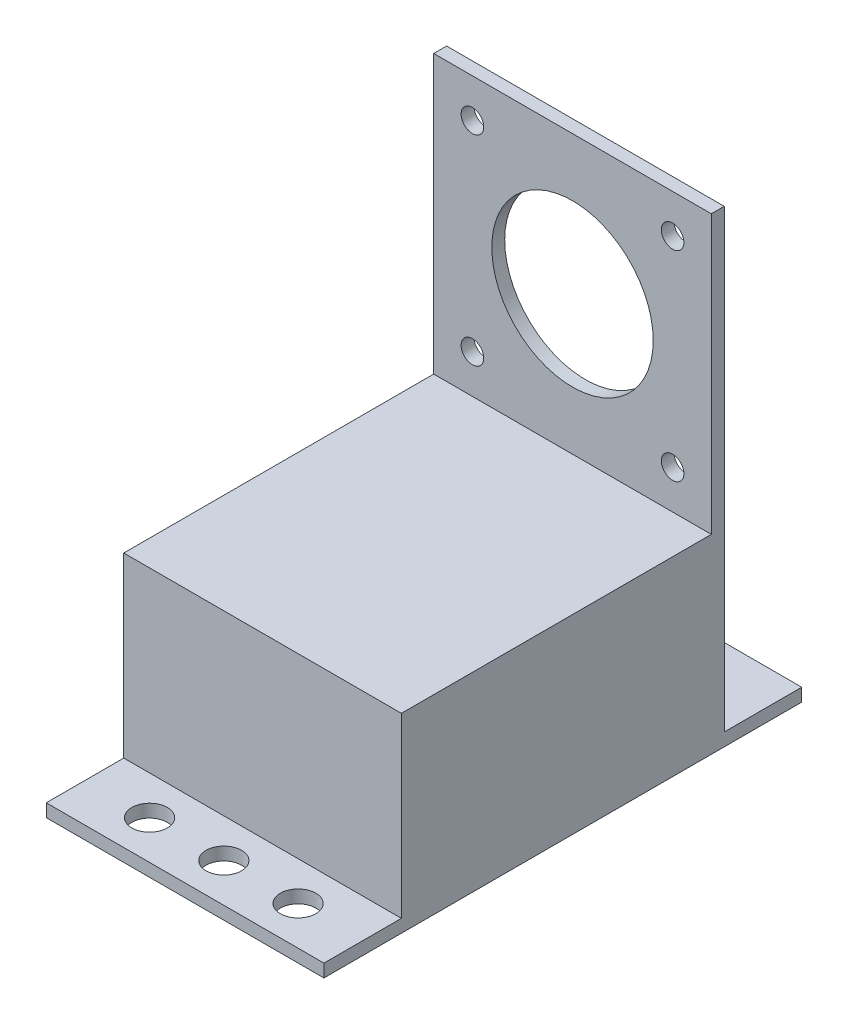
SolidWorks part; units mm, degrees
ref_plane "Front Plane" through (0, 0, 0) normal (0, 0, 1) x (1, 0, 0)
ref_plane "Top Plane" through (0, 0, 0) normal (0, 1, 0) x (1, 0, 0)
ref_plane "Right Plane" through (0, 0, 0) normal (1, 0, 0) x (0, 0, -1)
sketch "Sketch1" plane through (0, 0, 0) normal (0, 1, 0) x (1, 0, 0)
  line L0 (-21.5, 25) -> (21.5, 25)
  line L1 (-21.5, -37) -> (21.5, -37)
  line L2 (-21.5, -37) -> (-21.5, 37)
  line L3 (-21.5, 37) -> (21.5, 37)
  line L4 (21.5, -37) -> (21.5, 37)
  line L5 (-21.5, -37) -> (21.5, 37) construction
  line L6 (-21.5, 37) -> (21.5, -37) construction
  line L7 (-21.5, 23) -> (21.5, 23)
  line L8 (21.5, -25) -> (-21.5, -25) construction
  line L9 (0, 37) -> (0, -37) construction
  circle A0 centre (0, 31) radius 2.75
  circle A1 centre (0, -31) radius 2.75
  point P0 (0, 0)
  dimension "D6" = 6
  dimension "D7" = 5.5
  dimension "D8" = 5.5
  dimension "D9" = 6
  dimension "D1" = 12
  dimension "D2" = 2
  dimension "D3" = 43
  dimension "D4" = 48
  dimension "D5" = 12
extrude "Boss-Extrude1" add sketch "Sketch1" along normal blind 43 contours L2 L7 L4 L0 region at (0, 0, -24)
extrude "Boss-Extrude2" add sketch "Sketch1<3>" against normal blind 29.5 contours L4 L3 L2 L1
sketch "Sketch1<3>" plane through (0, 0, 0) normal (0, 1, 0) x (1, 0, 0) same geometry as "Sketch1"
sketch "Sketch2" plane through (0, 0, -23) normal (0, 0, 1) x (1, 0, 0)
  line L0 (-21.5, 43) -> (21.5, 43) construction
  line L1 (-15.5, 6) -> (15.5, 6) construction
  line L2 (-15.5, 6) -> (-15.5, 37) construction
  line L3 (-15.5, 37) -> (15.5, 37) construction
  line L4 (15.5, 6) -> (15.5, 37) construction
  line L5 (-15.5, 6) -> (15.5, 37) construction
  line L6 (-15.5, 37) -> (15.5, 6) construction
  line L7 (-21.5, 43) -> (-21.5, 0) construction
  line L8 (21.5, 43) -> (21.5, 0) construction
  line L9 (-21.5, 0) -> (21.5, 0) construction
  circle A0 centre (0, 21.5) radius 12.5
  circle A1 centre (-15.5, 37) radius 1.75
  circle A2 centre (15.5, 37) radius 1.75
  circle A3 centre (15.5, 6) radius 1.75
  circle A4 centre (-15.5, 6) radius 1.75
  point P0 (0, 21.5)
  point P25 (0, 21.5)
  point P26 (0, 21.5)
  dimension "D5" = 4
  dimension "D1" = 6
  dimension "D2" = 6
  dimension "D3" = 6
  dimension "D4" = 6
extrude "Cut-Extrude1" cut sketch "Sketch2" against normal up to next contours A0 | A1 | A3 | A4 | A2
extrude "Cut-Extrude2" cut sketch "Sketch1<4>" against normal up to next contours A0 | A1 region at (0, 0, -31) region at (0, 0, 31)
sketch "Sketch1<4>" plane through (0, 0, 0) normal (0, 1, 0) x (1, 0, 0) same geometry as "Sketch1"
pattern_linear "LPattern1" count 2 spacing 11.5 along (1, 0, 0) count 2 spacing 11.5 along (-1, 0, 0) of "Cut-Extrude2" pattern seed only yes
sketch "Sketch3" plane through (0, 0, 0) normal (0, 1, 0) x (1, 0, 0)
  line L0 (-21.5, -37) -> (-21.5, 23) construction
  line L1 (21.5, -37) -> (-21.5, -37)
  line L2 (21.5, -37) -> (21.5, -25)
  line L3 (21.5, -25) -> (-21.5, -25)
  line L4 (-21.5, -37) -> (-21.5, -25)
  line L6 (21.5, 37) -> (-21.5, 37)
  line L7 (21.5, 37) -> (21.5, 25)
  line L8 (21.5, 25) -> (-21.5, 25)
  line L9 (-21.5, 37) -> (-21.5, 25)
  dimension "D1" = 12
extrude "Cut-Extrude3" cut sketch "Sketch3" against normal blind 27.5
